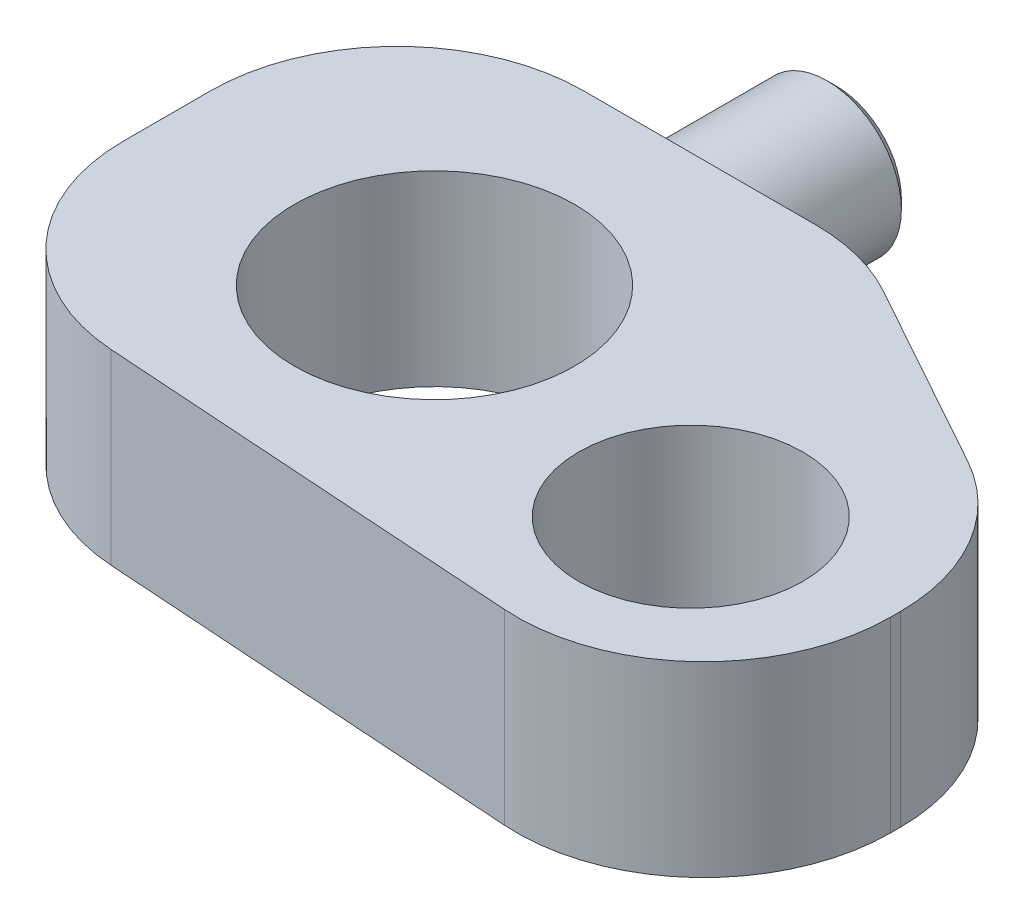
SolidWorks part; units mm, degrees
ref_plane "Front" through (0, 0, 0) normal (0, 0, 1) x (1, 0, 0)
ref_plane "Top" through (0, 0, 0) normal (0, 1, 0) x (1, 0, 0)
ref_plane "Right" through (0, 0, 0) normal (1, 0, 0) x (0, 0, -1)
sketch "Sketch1" plane through (0, 0, 0) normal (0, 0, 1) x (1, 0, 0)
  circle A0 centre (0, 0) radius 5
  dimension "D1" = 10
extrude "Boss-Extrude1" add sketch "Sketch1" along normal blind 20
sketch "Sketch2" plane through (0, 0, 0) normal (0, 0, -1) x (-1, 0, 0)
  circle A0 centre (0, 0) radius 3.98
  circle A1 centre (0, 0) radius 5 construction
  circle A2 centre (0, 0) radius 5
  dimension "D1" = 7.96
extrude "Cut-Extrude2" cut sketch "Sketch2" against normal blind 8 contours A0 | A2
chamfer "Chamfer1" distance 0.5 angle 45 1 edges at (-5, 0, 8)
chamfer "Chamfer2" distance 0.5 angle 45 1 edges at (-3.98, 0, 0)
sketch "Sketch8" plane through (0, 0, 20) normal (0, 0, 1) x (1, 0, 0)
  circle A0 centre (0, 0) radius 5
  dimension "D1" = 10
extrude "Boss-Extrude2" add sketch "Sketch8" along normal blind 20
sketch "Sketch9" plane through (0, 0, 40) normal (0, 0, 1) x (1, 0, 0)
  line L1 (0, 5) -> (35, 5)
  line L3 (0, -5) -> (35, -5)
  line L4 (35, 5) -> (35, -5)
  circle A1 centre (0, 0) radius 5 construction
  arc A2 (0, -5) -> (0, 5) centre (0, 0) ccw
  dimension "D1" = 35
  dimension "D2" = 5
  dimension "D3" = 10
extrude "Boss-Extrude3" add sketch "Sketch9" against normal blind 31.5
sketch "Sketch10" plane through (0, 0, 40) normal (0, 0, 1) x (1, 0, 0)
  line L5 (0, 5) -> (-15, 5)
  line L7 (0, -5) -> (-15, -5)
  line L8 (-15, 5) -> (-15, -5)
  arc A0 (0, 5) -> (0, -5) centre (0, 0) ccw construction
  arc A1 (0, 5) -> (0, -5) centre (0, 0) ccw
  arc M5 (0, 5) -> (0, -5) centre (0, 0) ccw
  dimension "D1" = 15
extrude "Boss-Extrude4" add sketch "Sketch10" against normal blind 31.5 contours M5 | L8 M5 region at (-9.4073, 0, 40)
sketch "Sketch12" plane through (0, 5, 0) normal (0, 1, 0) x (1, 0, 0)
  line L0 (0, -8.5) -> (-15, -8.5) construction
  line L3 (0, -21.5) -> (73.8631, -37.7534) construction
  line L4 (0, -21.5) -> (73.9968, -21.5) construction
  circle A0 centre (0, -21.5) radius 7.5
  circle A3 centre (17.5794, -25.3683) radius 6
  dimension "D1" = 15
  dimension "D3" = 12.41
  dimension "D4" = 12
  dimension "D2" = 13
  dimension "D5" = 18
extrude "Cut-Extrude3" cut sketch "Sketch12" against normal blind 31.5
sketch "Sketch14" plane through (0, 5, 0) normal (0, 1, 0) x (1, 0, 0)
  line L1 (35, -8.5) -> (0, -8.5) construction
  line L2 (35, -8.5) -> (35, -40) construction
  line L4 (-15, -8.5) -> (-15, -40) construction
  line L6 (-15, -40) -> (35, -40)
  line L7 (35, -40) -> (35, -37.3683)
  line L8 (27.5794, -35.3683) -> (-15, -32.5)
  line L9 (-15, -32.5) -> (-15, -40)
  line L10 (27.5794, -18.2519) -> (27.5794, -35.3683)
  line L11 (-15, -40) -> (35, -40)
  line L12 (35, -40) -> (35, -8.5)
  line L13 (35, -8.5) -> (0, -8.5)
  line L14 (0, -8.5) -> (-15, -8.5)
  line L15 (-15, -8.5) -> (-15, -40)
  line L18 (35, -8.5) -> (10, -8.5)
  line L22 (35, -37.3683) -> (35, -8.5)
  line L23 (10, -8.5) -> (27.5794, -18.2519)
  circle A0 centre (0, -21.5) radius 7.5 construction
  dimension "D2" = 10
  dimension "D3" = 11
  dimension "D4" = 7.1164
  dimension "D6" = 10
  dimension "D7" = 10
  dimension "D1" = 0
extrude "Cut-Extrude4" cut sketch "Sketch14" against normal through all
fillet "Fillet1" radius 10 5 edges at (-15, 0, 8.5) (-15, 0, 32.5) (27.5794, 0, 35.3683) (27.5794, 0, 18.2519) (10, 0, 8.5)
sketch "Sketch15" plane through (0, 5, 0) normal (0, 1, 0) x (1, 0, 0)
  line L0 (0, -21.5) -> (57.2418, -34.0932)
  line L1 (0, -21.5) -> (51.5086, -21.5)
  dimension "D1" = 12.407
